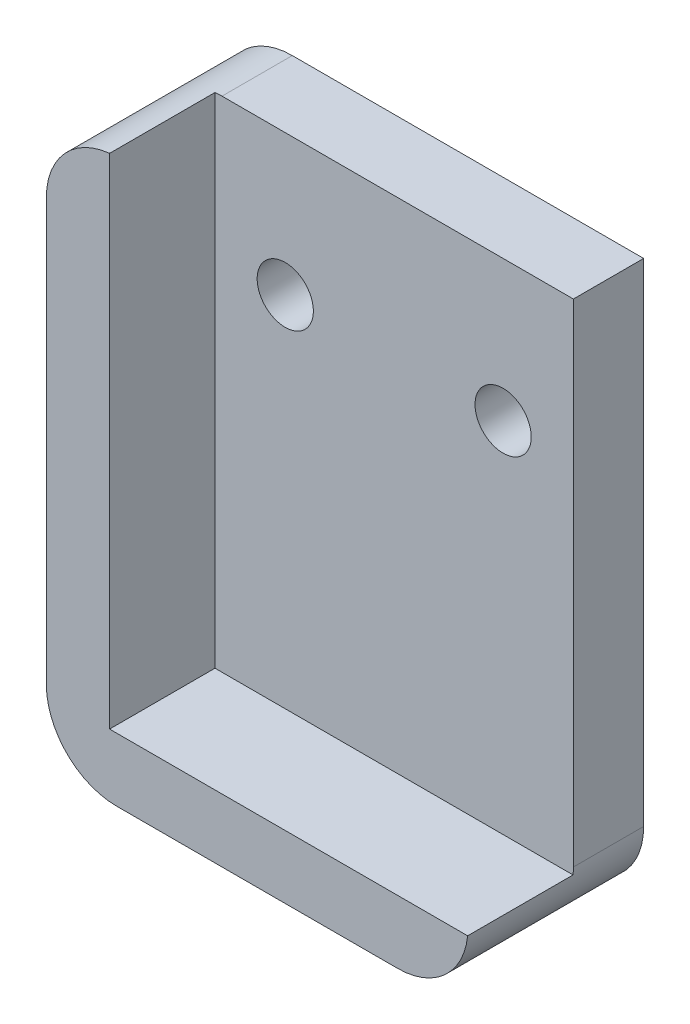
SolidWorks part; units mm, degrees
ref_plane "Front Plane" through (0, 0, 0) normal (0, 0, 1) x (1, 0, 0)
ref_plane "Top Plane" through (0, 0, 0) normal (0, 1, 0) x (1, 0, 0)
ref_plane "Right Plane" through (0, 0, 0) normal (1, 0, 0) x (0, 0, -1)
sketch "Sketch1" plane through (0, 0, 0) normal (0, 0, 1) x (1, 0, 0)
  line L0 (9, 80) -> (9, 9)
  line L1 (0, 0) -> (60, 0)
  line L2 (0, 0) -> (0, 80)
  line L5 (9, 9) -> (80, 9)
  line L7 (0, 80) -> (60, 80)
  line L8 (60, 80) -> (60, 0)
  circle A1 centre (50, 60) radius 2
  circle A2 centre (19, 60) radius 2
  circle A3 centre (19, 60) radius 4
  circle A4 centre (50, 60) radius 4
  dimension "D5" = 10
  dimension "D7" = 10
  dimension "D1" = 60
  dimension "D2" = 80
  dimension "D3" = 9
  dimension "D4" = 9
extrude "Boss-Extrude4" add sketch "Sketch1" along normal blind 10 contours L0 L5 A4 A3 | L5 L0 L2 L1 | A3 A2 | A2 | A4 A1 | A1 region at (34.5, 44.0574, 0) region at (8, 44.5, 0) region at (50, 60, 0) region at (19, 60, 0) region at (15.1131, 60, 0) region at (46.1131, 60, 0)
extrude "Boss-Extrude5" add sketch "Sketch1<12>" along normal blind 25 contours L5 L0 L2 L1 region at (8, 44.5, 0)
sketch "Sketch1<12>" plane through (0, 0, 0) normal (0, 0, 1) x (1, 0, 0) same geometry as "Sketch1"
extrude "Cut-Extrude1" cut sketch "Sketch1<15>" along normal blind 25 contours A2 | A1 region at (50, 60, 0) region at (19, 60, 0)
sketch "Sketch1<15>" plane through (0, 0, 0) normal (0, 0, 1) x (1, 0, 0) same geometry as "Sketch1"
extrude "Cut-Extrude2" cut sketch "Sketch1<16>" along normal blind 25 contours A4 A1 | A3 A2 region at (15.1131, 60, 0) region at (46.1131, 60, 0)
sketch "Sketch1<16>" plane through (0, 0, 0) normal (0, 0, 1) x (1, 0, 0) same geometry as "Sketch1"
extrude "Boss-Extrude7" add sketch "Sketch1<18>" along normal blind 4 contours A4 A1 | A3 A2 region at (15.1131, 60, 0) region at (46.1131, 60, 0)
sketch "Sketch1<18>" plane through (0, 0, 0) normal (0, 0, 1) x (1, 0, 0) same geometry as "Sketch1"
fillet "Fillet1" radius 10 3 edges at (60, 0, 12.5) (0, 80, 12.5) (0, 0, 12.5)
